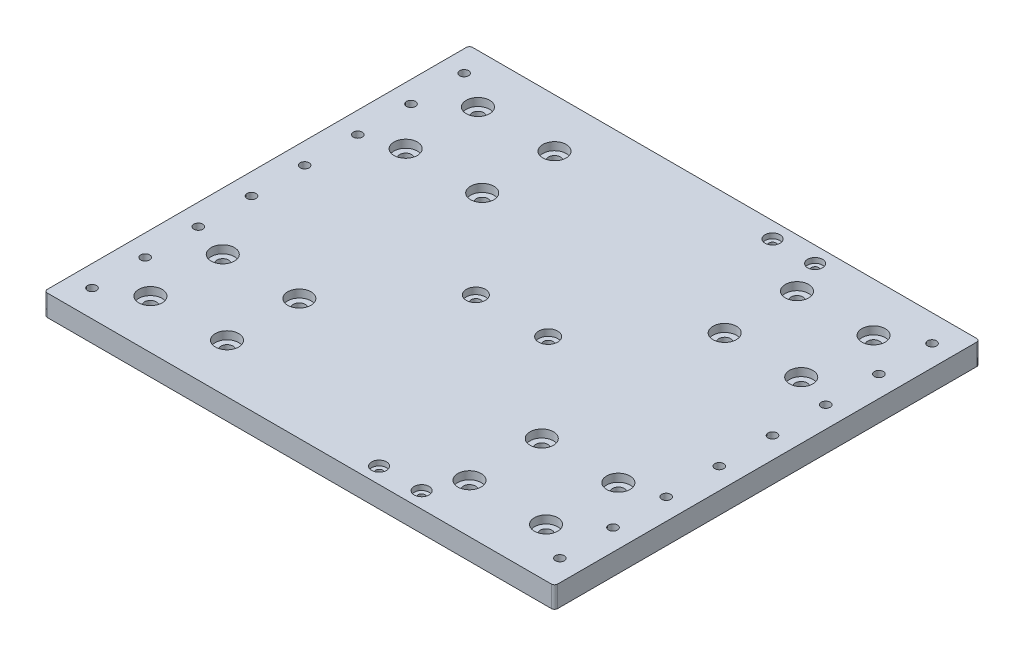
SolidWorks part; units mm, degrees
ref_plane "Front Plane" through (0, 0, 0) normal (0, 0, 1) x (1, 0, 0)
ref_plane "Top Plane" through (0, 0, 0) normal (0, 1, 0) x (1, 0, 0)
ref_plane "Right Plane" through (0, 0, 0) normal (1, 0, 0) x (0, 0, -1)
sketch "Sketch1" plane through (0, 0, 0) normal (0, 1, 0) x (1, 0, 0)
  line L1 (-120, -100) -> (120, -100)
  line L2 (-120, -100) -> (-120, 100)
  line L3 (-120, 100) -> (120, 100)
  line L4 (120, -100) -> (120, 100)
  line L5 (-120, -100) -> (120, 100) construction
  line L6 (-120, 100) -> (120, -100) construction
  point P0 (0, 0)
  dimension "D1" = 240
  dimension "D2" = 200
extrude "Boss-Extrude1" add sketch "Sketch1" along normal mid plane 10
hole_wizard "CBORE for M5 Pan Head Machine Screw1" positions "Sketch11" profile "Sketch10" counterbore size "M5" standard "ANSI Metric" end condition through all
sketch "Sketch11" plane through (66.9231, 5, -81.9693) normal (0, -1, 0) x (-1, 0, 0)
  line L0 (141.9231, -1018.8886) -> (141.9231, 48981.1114) construction
  line L1 (-912.3245, -141.9693) -> (49087.6755, -141.9693) construction
  line L2 (186.9231, 18.0307) -> (186.9231, -181.9693) construction
  line L3 (186.9231, -181.9693) -> (-53.0769, -181.9693) construction
  line L5 (159.9231, -124.9693) -> (123.9231, -124.9693) construction
  line L6 (159.9231, -124.9693) -> (159.9231, -158.9693) construction
  line L7 (159.9231, -158.9693) -> (123.9231, -158.9693) construction
  line L8 (123.9231, -124.9693) -> (123.9231, -158.9693) construction
  line L9 (159.9231, -124.9693) -> (123.9231, -158.9693) construction
  line L10 (159.9231, -158.9693) -> (123.9231, -124.9693) construction
  point P0 (159.9231, -158.9693)
  point P2 (123.9231, -158.9693)
  point P4 (123.9231, -124.9693)
  point P6 (159.9231, -124.9693)
  dimension "D1" = 45
  dimension "D2" = 40
  dimension "D3" = 18
  dimension "D4" = 34
  dimension "D5" = 17
  dimension "D6" = 36
sketch "Sketch10" plane through (-93, 5, 77) normal (1, 0, 0) x (0, 0, 1)
  line L0 (0, 0) -> (0, 10)
  line L1 (0, 10) -> (2.75, 10)
  line L3 (2.75, 10) -> (2.75, 3.7)
  line L4 (2.75, 3.7) -> (5.5, 3.7)
  line L5 (5.5, 3.7) -> (5.5, 0)
  line L7 (5.5, 0) -> (0, 0)
  line L11 (0, -6.35) -> (0, 107.95) construction
  dimension "Thru Hole Dia." = 5.5
  dimension "Thru Hole Depth" = 10
  dimension "C'Bore Dia." = 11
  dimension "C'Bore Depth" = 3.7
mirror "Mirror1" about plane through (0, 0, 0) normal (1, 0, 0) of "CBORE for M5 Pan Head Machine Screw1"
mirror "Mirror2" about plane through (0, 0, 0) normal (0, 0, 1) of "Mirror1"
hole_wizard "CBORE for M4 Pan Head Machine Screw1" positions "Sketch9" profile "Sketch8" counterbore size "M4" standard "ANSI Metric" end condition through all
sketch "Sketch9" plane through (-30.3385, 5, -23.5385) normal (0, -1, 0) x (-1, 0, 0)
  line L0 (-1000, -23.5385) -> (49000, -23.5385) construction
  point P0 (-13.3385, -23.5385)
  point P2 (-47.3385, -23.5385)
  dimension "D1" = 17
  dimension "D2" = 17
sketch "Sketch8" plane through (-17, 5, 0) normal (1, 0, 0) x (0, 0, 1)
  line L0 (0, 0) -> (0, 10)
  line L1 (0, 10) -> (2.25, 10)
  line L3 (2.25, 10) -> (2.25, 3.1)
  line L4 (2.25, 3.1) -> (4.5, 3.1)
  line L5 (4.5, 3.1) -> (4.5, 0)
  line L7 (4.5, 0) -> (0, 0)
  line L11 (0, -6.35) -> (0, 107.95) construction
  dimension "Thru Hole Dia." = 4.5
  dimension "Thru Hole Depth" = 10
  dimension "C'Bore Dia." = 9
  dimension "C'Bore Depth" = 3.1
hole_wizard "M5x0.8 Tapped Hole1" positions "Sketch7" profile "Sketch5" tap size "M5x0.8" standard "ANSI Metric" end condition through all
sketch "Sketch7" plane through (0, 5, 0) normal (0, 1, 0) x (1, 0, 0)
  line L0 (120, 100) -> (-120, 100) construction
  line L1 (-120, 100) -> (-120, -100) construction
  line L2 (120, -100) -> (120, 100) construction
  point P0 (-110, 87.5)
  point P2 (110, 87.5)
  dimension "D1" = 12.5
  dimension "D2" = 10
  dimension "D3" = 10
  dimension "D4" = 12.5
sketch "Sketch5" plane through (-110, 5, -87.5) normal (1, 0, 0) x (0, 0, 1)
  line L0 (0, 0) -> (0, 10)
  line L1 (0, 10) -> (2.1, 10)
  line L2 (2.1, 10) -> (2.1, 0)
  line L5 (2.1, 0) -> (0, 0)
  line L11 (0, -6.35) -> (0, 107.95) construction
  dimension "Thru Tap Drill Dia." = 4.2
  dimension "Thru Tap Drill Depth" = 10
cosmetic thread "Hole Thread1" parameters "D2"=5
cosmetic thread "Hole Thread2" parameters "D2"=5
fillet "Fillet1" radius 1.5 4 edges at (-120, 0, -100) (120, 0, -100) (-120, 0, 100) (120, 0, 100)
pattern_linear "LPattern2" count 8 spacing 25 along (0, 0, 1) of "M5x0.8 Tapped Hole1"
hole_wizard "CBORE for M3 Pan Head Machine Screw1" positions "Sketch13" profile "Sketch12" counterbore size "M3" standard "ANSI Metric" end condition through all
sketch "Sketch13" plane through (0, 5, 0) normal (0, 1, 0) x (1, 0, 0)
  line L0 (118.5, 100) -> (-118.5, 100) construction
  point P0 (30, 92.5)
  point P2 (50, 92.5)
  dimension "D1" = 50
  dimension "D2" = 20
  dimension "D3" = 7.5
  dimension "D4" = 7.5
sketch "Sketch12" plane through (30, 5, -92.5) normal (1, 0, 0) x (0, 0, 1)
  line L0 (0, 0) -> (0, 10)
  line L1 (0, 10) -> (1.6, 10)
  line L3 (1.6, 10) -> (1.6, 2.4)
  line L4 (1.6, 2.4) -> (3.5, 2.4)
  line L5 (3.5, 2.4) -> (3.5, 0)
  line L7 (3.5, 0) -> (0, 0)
  line L11 (0, -6.35) -> (0, 107.95) construction
  dimension "Thru Hole Dia." = 3.2
  dimension "Thru Hole Depth" = 10
  dimension "C'Bore Dia." = 7
  dimension "C'Bore Depth" = 2.4
mirror "Mirror3" about plane through (0, 0, 0) normal (0, 0, 1) of "CBORE for M3 Pan Head Machine Screw1"
equation "\"D5@Sketch11\"=\"D4@Sketch11\"/2"
equation "\"D3@Sketch11\"=\"D6@Sketch11\"/2"
